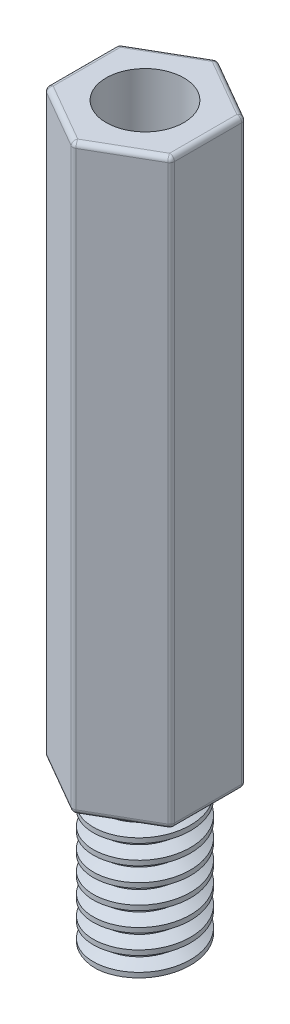
SolidWorks part; units mm, degrees
ref_plane "前视基准面" through (0, 0, 0) normal (0, 0, 1) x (1, 0, 0)
ref_plane "上视基准面" through (0, 0, 0) normal (0, 1, 0) x (1, 0, 0)
ref_plane "右视基准面" through (0, 0, 0) normal (1, 0, 0) x (0, 0, -1)
sketch "草图1" plane through (0, 0, 0) normal (0, 1, 0) x (1, 0, 0)
  line L0 (-1.299, 0.75) -> (1.299, -0.75) construction
  line L1 (1.299, 0.75) -> (-1.299, -0.75) construction
  line L2 (0, 1.5) -> (0, -1.5) construction
  line L3 (-1.299, 0.75) -> (0, 1.5)
  line L4 (0, 1.5) -> (1.299, 0.75)
  line L5 (1.299, 0.75) -> (1.299, -0.75)
  line L6 (1.299, -0.75) -> (0, -1.5)
  line L7 (0, -1.5) -> (-1.299, -0.75)
  line L8 (-1.299, -0.75) -> (-1.299, 0.75)
  circle A0 centre (0, 0) radius 1.5 construction
  point P12 (0, 0)
extrude "凸台-拉伸1" add sketch "草图1" along normal blind 15
sketch "草图2" plane through (0, 15, 0) normal (0, 1, 0) x (1, 0, 0)
  circle A0 centre (0, 0) radius 1
hole_wizard "M2 螺纹孔1" positions "草图3" profile "草图4" tap size "M2" standard "ISO"
sketch "草图3" plane through (0, 15, 0) normal (0, 1, 0) x (1, 0, 0)
  point P0 (0, 0)
sketch "草图4" plane through (0, 15, 0) normal (1, 0, 0) x (0, 0, 1)
  line L0 (0, 0) -> (0, 3.9807)
  line L1 (0, 3.9807) -> (0.8, 3.5)
  line L2 (0.8, 3.5) -> (0.8, 0)
  line L5 (0.8, 0) -> (0, 0)
  line L10 (0, 3.9807) -> (-0.8, 3.5) construction
  line L11 (0, -6.35) -> (0, 107.95) construction
  dimension "螺纹孔钻头直径" = 1.6
  dimension "螺纹孔钻头深度" = 3.5
  dimension "导头角度" = 118
cosmetic thread "孔螺蚊线1" parameters "D1"=3.5, "D2"=2
sketch "草图6" plane through (0, 0, 0) normal (0, -1, 0) x (1, 0, 0)
  circle A0 centre (0, 0) radius 1
  circle A1 centre (0, 0) radius 1.9435
extrude "切除-拉伸1" cut sketch "草图6" against normal blind 3
thread "螺纹线1" pitch 0.4 method cut profile "螺纹线轮廓2" start angle 0, offset 1, length 3.8, pitch 0.4, diameter 2
ref_plane "基准面2" through (1, -1, 0) normal (0, 0, 1) x (1, 0, 0)
sketch "螺纹线轮廓2" plane through (1, -1, 0) normal (0, 0, 1) x (1, 0, 0)
  line L0 (0, 0) -> (0, 0.4) construction
  line L1 (0, 0.3) -> (-0.2165, 0.175)
  line L2 (-0.2165, 0.175) -> (-0.2165, 0.125)
  line L3 (-0.2165, 0.125) -> (0, 0)
  line L4 (-0.2165, 0.15) -> (0, 0.15) construction
  line L11 (0, 0.3) -> (0, 0)
  point P6 (0, 0)
  dimension "Pitch" = 0.4
  dimension "Profile_Angle" = 60
  dimension "Profile_Land" = 0.05
  dimension "Profile_Height" = 0.2165
fillet "圆角1" radius 0.1 18 edges at (1.299, 3, 0) (0.6495, 3, -1.125) (0.6495, 3, 1.125) (-1.299, 3, 0) (-0.6495, 3, 1.125) (-0.6495, 15, -1.125) (0.6495, 15, -1.125) (1.299, 15, 0) (0.6495, 15, 1.125) (-0.6495, 15, 1.125) (-1.299, 15, 0) (0, 9, 1.5) (-1.299, 9, 0.75) (-1.299, 9, -0.75) (0, 9, -1.5) (1.299, 9, 0.75) (1.299, 9, -0.75) (-0.6495, 3, -1.125)
